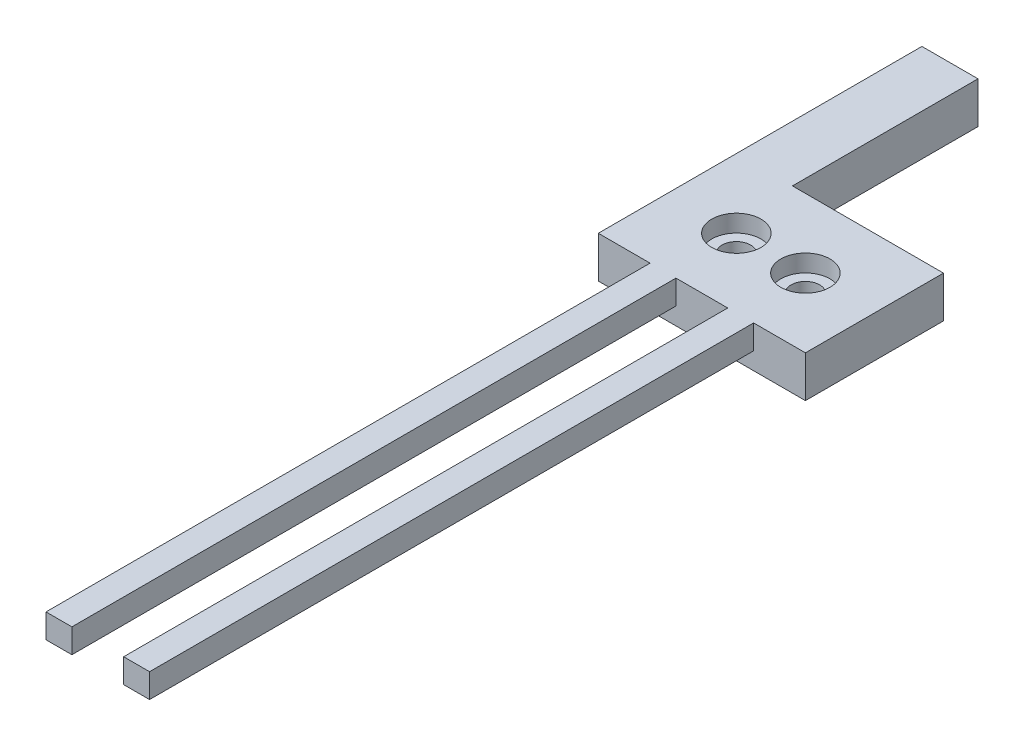
SolidWorks part; units mm, degrees
ref_plane "Front Plane" through (0, 0, 0) normal (0, 0, 1) x (1, 0, 0)
ref_plane "Top Plane" through (0, 0, 0) normal (0, 1, 0) x (1, 0, 0)
ref_plane "Right Plane" through (0, 0, 0) normal (1, 0, 0) x (0, 0, -1)
sketch "Sketch1" plane through (0, 0, 0) normal (0, -1, 0) x (1, 0, 0)
  line L0 (0, -8) -> (8, -8) construction
  line L1 (0, 0) -> (24, 0)
  line L2 (0, 0) -> (0, -16)
  line L3 (0, -16) -> (24, -16)
  line L4 (24, 0) -> (24, -16)
  line L5 (8, -8) -> (16, -8) construction
  line L6 (16, -8) -> (24, -8) construction
  circle A0 centre (8, -8) radius 1.65
  circle A1 centre (16, -8) radius 1.65
  dimension "D3" = 3.3
  dimension "D1" = 16
  dimension "D2" = 24
extrude "Boss-Extrude1" add sketch "Sketch1" along normal blind 4.8
sketch "Sketch2" plane through (0, 0, 0) normal (0, 0, 1) x (1, 0, 0)
  line L0 (24, 0) -> (0, 0) construction
  line L1 (6, 0) -> (9, 0)
  line L2 (6, 0) -> (6, -2.8)
  line L3 (6, -2.8) -> (9, -2.8)
  line L4 (9, 0) -> (9, -2.8)
  line L5 (0, 0) -> (6, 0) construction
  line L6 (15, 0) -> (18, 0)
  line L7 (15, 0) -> (15, -2.8)
  line L8 (15, -2.8) -> (18, -2.8)
  line L9 (18, 0) -> (18, -2.8)
  line L10 (9, 0) -> (15, 0) construction
  line L11 (18, 0) -> (24, 0) construction
  dimension "D1" = 2.8
  dimension "D2" = 3
  dimension "D3" = 3
extrude "Boss-Extrude2" add sketch "Sketch2" along normal blind 70
sketch "Sketch3" plane through (0, 0, 0) normal (0, 1, 0) x (1, 0, 0)
  circle A0 centre (8, 8) radius 2.85
  circle A1 centre (16, 8) radius 2.85
  dimension "D1" = 5.7
extrude "Cut-Extrude1" cut sketch "Sketch3" against normal blind 2
sketch "Sketch4" plane through (0, 0, 0) normal (0, 1, 0) x (1, 0, 0)
  line L0 (6.5, 37.5) -> (0, 37.5)
  line L1 (0, 37.5) -> (0, 16)
  line L2 (0, 16) -> (6.5, 16)
  line L3 (0, 16) -> (24, 16) construction
  line L4 (6.5, 16) -> (6.5, 37.5)
extrude "Boss-Extrude3" add sketch "Sketch4" against normal blind 4.8
